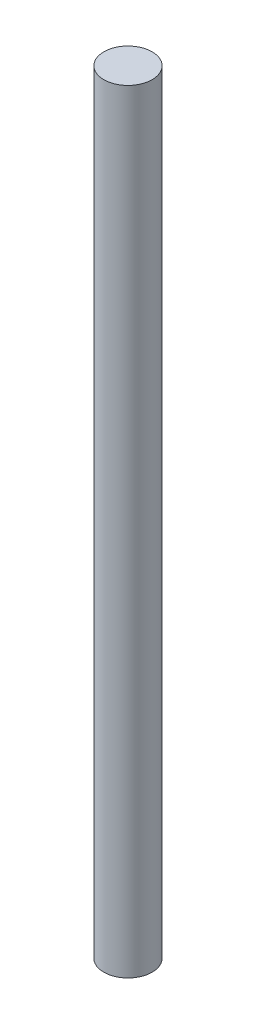
SolidWorks part; units mm, degrees
ref_plane "Front Plane" through (0, 0, 0) normal (0, 0, 1) x (1, 0, 0)
ref_plane "Top Plane" through (0, 0, 0) normal (0, 1, 0) x (1, 0, 0)
ref_plane "Right Plane" through (0, 0, 0) normal (1, 0, 0) x (0, 0, -1)
sketch "Sketch1" plane through (0, 0, 0) normal (0, 1, 0) x (1, 0, 0)
  circle A0 centre (0, 0) radius 6.35
extrude "Boss-Extrude1" add sketch "Sketch1" along normal blind 203.2
